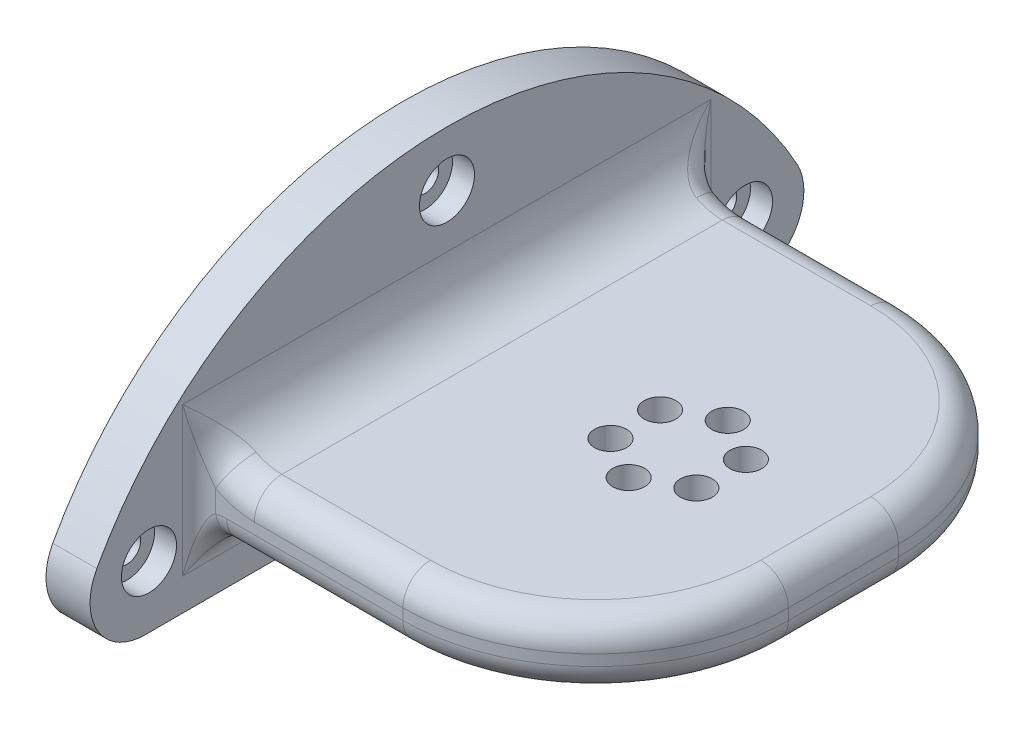
SolidWorks part; units mm, degrees
ref_plane "Front Plane" through (0, 0, 0) normal (0, 0, 1) x (1, 0, 0)
ref_plane "Top Plane" through (0, 0, 0) normal (0, 1, 0) x (1, 0, 0)
ref_plane "Right Plane" through (0, 0, 0) normal (1, 0, 0) x (0, 0, -1)
sketch "Sketch1" plane through (0, 0, 0) normal (1, 0, 0) x (0, 0, -1)
  line L0 (0, 0) -> (0, 47021.9982) construction
  line L1 (0, 0) -> (47021.9982, 0) construction
  line L2 (-54.8293, 20) -> (54.8293, 20)
  line L3 (0, 30.825) -> (50000, 30.825) construction
  line L5 (-45, 30.825) -> (45, 30.825)
  line L6 (-45, 30.825) -> (-45, 42.825)
  line L7 (-45, 42.825) -> (45, 42.825)
  line L8 (45, 30.825) -> (45, 42.825)
  arc A0 (58.9121, 20.8714) -> (-58.9121, 20.8714) centre (0, 0) ccw construction
  circle A7 centre (0, 62.5) radius 2.5
  circle A8 centre (54.1266, 31.25) radius 2.5
  circle A9 centre (54.1266, -31.25) radius 2.5 [skipped]
  arc A10 (63.602, 34.8) -> (-63.602, 34.8) centre (0, 0) ccw
  arc A11 (54.8293, 20) -> (63.602, 34.8) centre (54.8293, 30) ccw
  arc A12 (-54.8293, 20) -> (-63.602, 34.8) centre (-54.8293, 30) cw
  circle A13 centre (0, -62.5) radius 2.5 [skipped]
  circle A14 centre (-54.1266, -31.25) radius 2.5 [skipped]
  circle A15 centre (-54.1266, 31.25) radius 2.5
  point P21 (0, 0)
  point P36 (0, 0)
  dimension "D1" = 125
  dimension "D2" = 5
  dimension "D4" = 145
  dimension "D6" = 10
  dimension "D3" = 6
  dimension "D5" = 20
  dimension "D7" = 30.825
  dimension "D8" = 90
  dimension "D9" = 12
extrude "Boss-Extrude1" add sketch "Sketch1" along normal blind 8 contours L5 L8 L7 L6 | A12 L2 A11 A10 L8 L5 L6 L7 region at (0, 43.6184, 0) region at (0, 36.825, 0)
extrude "Boss-Extrude2" add sketch "Sketch1<3>" along normal blind 80 contours L5 L8 L7 L6 region at (0, 36.825, 0)
sketch "Sketch1<3>" plane through (0, 0, 0) normal (1, 0, 0) x (0, 0, -1) same geometry as "Sketch1"
fillet "Fillet1" radius 35 2 edges at (80, 36.825, 45) (80, 36.825, -45)
fillet "Fillet2" radius 3 2 edges at (8, 36.825, 45) (8, 36.825, -45)
sketch "Sketch2" plane through (8, 0, 0) normal (1, 0, 0) x (0, 0, -1)
  circle A0 centre (0, 62.5) radius 5
  circle A1 centre (54.1266, 31.25) radius 5
  circle A2 centre (-54.1266, 31.25) radius 5
  dimension "D1" = 10
extrude "Cut-Extrude1" cut sketch "Sketch2" against normal blind 4
fillet "Fillet3" radius 10 1 edges at (8, 42.825, 0)
sketch "Sketch3" plane through (0, 30.825, 0) normal (0, -1, 0) x (1, 0, 0)
  line L1 (80, 10) -> (80, -10) construction
  circle A0 centre (50, 0) radius 23.65
  circle A1 centre (50, 0) radius 14.85
  dimension "D1" = 47.3
  dimension "D2" = 29.7
  dimension "D3" = 30
extrude "Cut-Extrude2" cut sketch "Sketch3" against normal blind 8
sketch "Sketch4" plane through (0, 30.825, 0) normal (0, -1, 0) x (1, 0, 0)
  circle A0 centre (50, 0) radius 9 construction
  circle A1 centre (50, 9) radius 1.5
  circle A2 centre (57.7942, 4.5) radius 1.5
  circle A3 centre (57.7942, -4.5) radius 1.5
  circle A4 centre (50, -9) radius 1.5
  circle A5 centre (42.2058, -4.5) radius 1.5
  circle A6 centre (42.2058, 4.5) radius 1.5
  point P17 (50, 0)
  dimension "D1" = 18
  dimension "D2" = 3
  dimension "D3" = 6
extrude "Cut-Extrude3" cut sketch "Sketch4" against normal up to next
sketch "Sketch5" plane through (0, 42.825, 0) normal (0, 1, 0) x (1, 0, 0)
  circle A0 centre (50, 9) radius 2.9
  circle A1 centre (57.7942, 4.5) radius 2.9
  circle A2 centre (57.7942, -4.5) radius 2.9
  circle A3 centre (50, -9) radius 2.9
  circle A4 centre (42.2058, -4.5) radius 2.9
  circle A5 centre (42.2058, 4.5) radius 2.9
  dimension "D1" = 5.8
extrude "Cut-Extrude4" cut sketch "Sketch5" against normal blind 7
fillet "Fillet4" radius 5 1 edges at (8, 30.825, 0)
fillet "Fillet5" radius 5 9 edges at (9.0572, 28.8998, -45.7141) (11.9785, 30.7195, -45) (29, 30.825, -45) (9.0572, 28.8998, 45.7141) (11.9785, 30.7195, 45) (29, 30.825, 45) (69.7487, 30.825, 34.7487) (80, 30.825, 0) (69.7487, 30.825, -34.7487)
fillet "Fillet6" radius 5 9 edges at (9.7352, 47.1954, 45.2797) (14.2194, 43.5672, 45) (31.5, 42.825, 45) (9.7352, 47.1954, -45.2797) (14.2194, 43.5672, -45) (31.5, 42.825, -45) (69.7487, 42.825, -34.7487) (80, 42.825, 0) (69.7487, 42.825, 34.7487)
